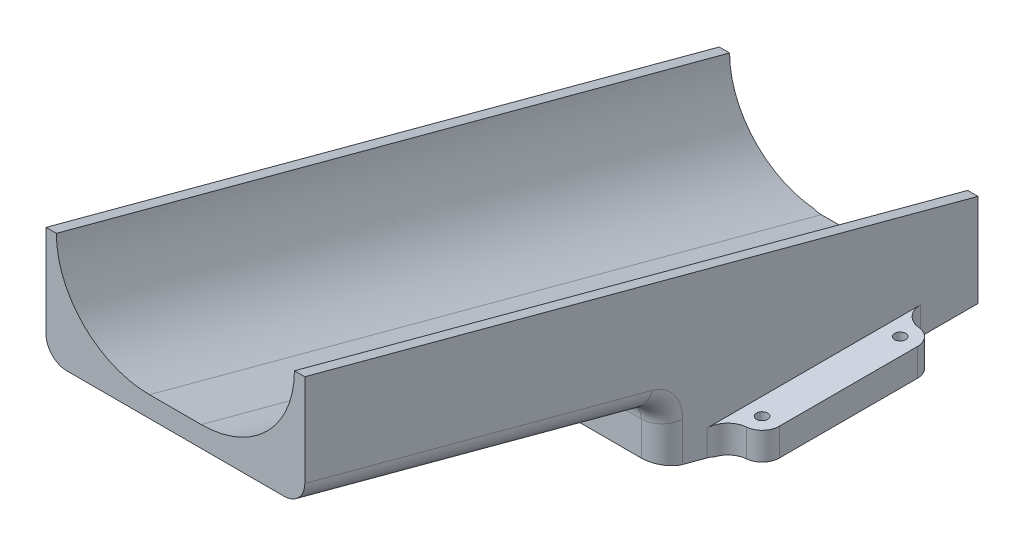
SolidWorks part; units mm, degrees
material "ABS"
ref_plane "Front Plane" through (0, 0, 0) normal (0, 0, 1) x (1, 0, 0)
ref_plane "Top Plane" through (0, 0, 0) normal (0, 1, 0) x (1, 0, 0)
ref_plane "Right Plane" through (0, 0, 0) normal (1, 0, 0) x (0, 0, -1)
sketch "Sketch1" plane through (0, 0, 0) normal (0, 0, 1) x (1, 0, 0)
  line L0 (-37.5, 0) -> (37.5, 0)
  line L1 (-37.5, 0) -> (-37.5, 30)
  line L2 (7.5, 3) -> (-7.5, 3)
  line L3 (-37.5, 30) -> (-34.5, 30)
  line L4 (0, 0) -> (0, 30) construction
  line L5 (37.5, 30) -> (34.5, 30)
  line L6 (37.5, 0) -> (37.5, 30)
  arc A0 (-34.5, 30) -> (-7.5, 3) centre (-7.5, 30) ccw
  arc A1 (34.5, 30) -> (7.5, 3) centre (7.5, 30) cw
  point P13 (0, 3)
  dimension "D1" = 3
  dimension "D2" = 75
  dimension "D3" = 3
  dimension "D4" = 30
sketch "Sketch2" plane through (0, 0, 0) normal (1, 0, 0) x (0, 0, -1)
  line L0 (0, 0) -> (-30.3779, 8.1397)
  line L1 (0, 0) -> (-8.2918, 0) construction
  dimension "D1" = 15
extrude "Boss-Extrude1" add sketch "Sketch1" along direction (0, 0.2588, 0.9659) on the side of the normal blind 190
sketch "Sketch3" plane through (0, 0, 0) normal (1, 0, 0) x (0, 0, -1)
  line L0 (-80, 18.4359) -> (-80, 0)
  line L1 (-80, 0) -> (0, 0)
  line L2 (0, 0) -> (-100, 26.7949)
  line L3 (-183.5259, 49.1756) -> (0, 0) construction
  line L4 (-183.5259, 49.1756) -> (-183.5259, 46.1756)
  line L5 (-183.5259, 46.1756) -> (-80, 18.4359)
  line L6 (-183.5259, 49.1756) -> (-100, 26.7949)
  dimension "D1" = 80
  dimension "D2" = 3
extrude "Boss-Extrude2" add sketch "Sketch3" along normal mid plane 75
extrude "Boss-Extrude5" add sketch "Sketch1<2>" along direction (0, 0.2588, 0.9659) on the side against the normal blind 12
sketch "Sketch1<2>" plane through (0, 0, 0) normal (0, 0, 1) x (1, 0, 0) same geometry as "Sketch1"
sketch "Sketch8" plane through (0, 0, 0) normal (0, 0, 1) x (1, 0, 0)
  line L1 (-37.5, 0) -> (37.5, 0)
  line L2 (-37.5, 0) -> (-37.5, -3.1058)
  line L3 (-37.5, -3.1058) -> (37.5, -3.1058)
  line L4 (37.5, 0) -> (37.5, -3.1058)
extrude "Cut-Extrude2" cut sketch "Sketch8" against normal blind 30
sketch "Sketch4" plane through (0, 0, 0) normal (0, 1, 0) x (1, 0, 0)
  line L0 (-37.5, -10.9737) -> (-42.5, -10.9737)
  line L1 (-37.5, -183.5259) -> (-37.5, 11.5911) construction
  line L2 (-47.5, -15.9737) -> (-47.5, -55.9737)
  line L3 (-47.5, -35.9737) -> (-37.5, -35.9737) construction
  line L4 (-37.5, -10.9737) -> (-37.5, -60.9737)
  line L5 (-37.5, -60.9737) -> (-42.5, -60.9737)
  line L6 (0, -43.5466) -> (0, 43.5466) construction
  line L7 (37.5, -10.9737) -> (42.5, -10.9737)
  line L8 (47.5, -15.9737) -> (47.5, -55.9737)
  line L9 (37.5, -60.9737) -> (42.5, -60.9737)
  line L10 (37.5, -10.9737) -> (37.5, -60.9737)
  circle A0 centre (-42.5, -15.9737) radius 1.6
  arc A1 (-42.5, -10.9737) -> (-47.5, -15.9737) centre (-42.5, -15.9737) ccw
  circle A2 centre (-42.5, -55.9737) radius 1.6
  arc A3 (-42.5, -60.9737) -> (-47.5, -55.9737) centre (-42.5, -55.9737) cw
  circle A4 centre (42.5, -15.9737) radius 1.6
  circle A5 centre (42.5, -55.9737) radius 1.6
  arc A6 (42.5, -10.9737) -> (47.5, -15.9737) centre (42.5, -15.9737) cw
  arc A7 (42.5, -60.9737) -> (47.5, -55.9737) centre (42.5, -55.9737) ccw
  dimension "D1" = 3.2
  dimension "D2" = 5
  dimension "D3" = 5
  dimension "D4" = 40
extrude "Boss-Extrude3" add sketch "Sketch4" along normal blind 8
chamfer "Chamfer2" distance 4 angle 75 1 edges at (0, 0, 80) first distance on face at (0, 9.218, 80)
fillet "Fillet1" radius 6 9 edges at (37.5, 32.3058, 131.763) (-37.5, 32.3058, 131.763) (37.5, 4, 60.9737) (37.5, 4, 10.9737) (-37.5, 4, 10.9737) (-37.5, 4, 60.9737) (37.5, 11.218, 80) (0, 18.4359, 80) (-37.5, 11.218, 80)
sketch "Sketch5" plane through (0, 0, 0) normal (0, 1, 0) x (1, 0, 0)
  line L1 (-45.4262, 4.2169) -> (43.7185, 4.2169)
  line L2 (-45.4262, 4.2169) -> (-45.4262, -3.1264)
  line L3 (-45.4262, -3.1264) -> (43.7185, -3.1264)
  line L4 (43.7185, 4.2169) -> (43.7185, -3.1264)
